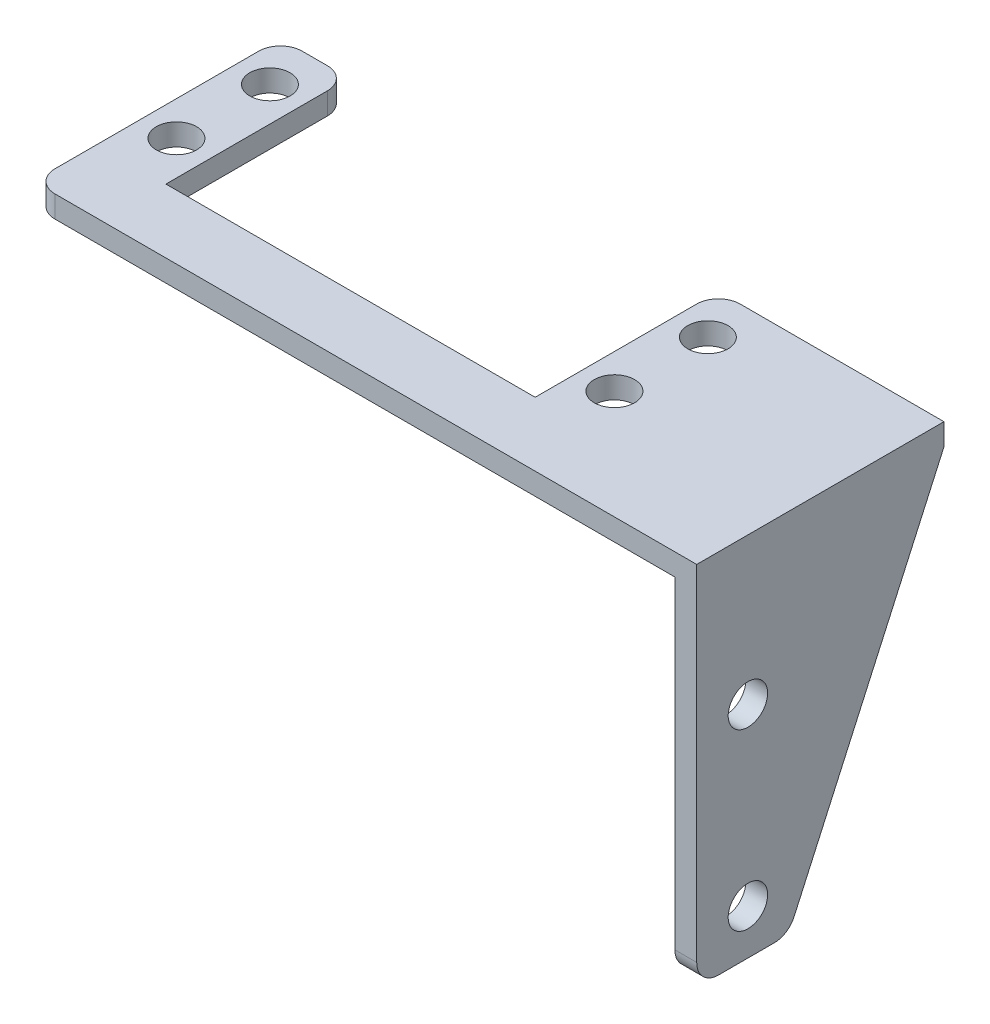
SolidWorks part; units mm, degrees
ref_plane "Front Plane" through (0, 0, 0) normal (0, 0, 1) x (1, 0, 0)
ref_plane "Top Plane" through (0, 0, 0) normal (0, 1, 0) x (1, 0, 0)
ref_plane "Right Plane" through (0, 0, 0) normal (1, 0, 0) x (0, 0, -1)
sketch "Sketch1" plane through (0, 0, 0) normal (0, 1, 0) x (1, 0, 0)
  line L0 (20.15, 0) -> (-20.15, 0)
  line L1 (-20.15, 0) -> (-20.15, 20)
  line L2 (-20.15, 20) -> (-27.65, 20)
  line L3 (-27.65, 20) -> (-27.65, -6.985)
  line L4 (-27.65, -6.985) -> (27.65, -6.985)
  line L5 (0, 0) -> (0, -6.985)
  line L6 (20.15, 20) -> (42.3837, 20)
  line L7 (42.3837, 20) -> (42.3837, -6.985)
  line L8 (20.15, 0) -> (20.15, 20)
  line L9 (27.65, -6.985) -> (42.3837, -6.985)
  circle A0 centre (-23.9, 15.1) radius 2.2
  circle A1 centre (-23.9, 4.9) radius 2.2
  circle A2 centre (23.9, 4.9) radius 2.2
  circle A3 centre (23.9, 15.1) radius 2.2
  point P0 (0, 0)
  dimension "D3" = 4.4
  dimension "D6" = 4.4
  dimension "D1" = 3.75
  dimension "D2" = 3.75
  dimension "D4" = 4.9
  dimension "D5" = 10.2
  dimension "D7" = 4.9
  dimension "D8" = 6.985
  dimension "D9" = 23.9
  dimension "D10" = 0
  dimension "D11" = 22.2338
extrude "Boss-Extrude1" add sketch "Sketch1" along normal blind 2.3813 contours L5 L0 L1 L2 L3 L4 A1 A0 | L8 L0 L5 L4 A2 A3 region at (27.3831, 0, -4.3765) region at (-0.3864, 0, 3.4925)
sketch "Sketch3" plane through (42.3837, 0, 0) normal (1, 0, 0) x (0, 0, -1)
  line L0 (20, 0) -> (3.015, -37.6187)
  line L1 (20, 2.3813) -> (-6.985, 2.3813)
  line L2 (20, 2.3813) -> (20, 0)
  line L3 (3.015, -37.6187) -> (-6.985, -37.6187)
  line L4 (-6.985, 2.3813) -> (-6.985, -37.6187)
  line L5 (-6.985, 2.3813) -> (-6.985, 0) construction
  point P10 (-6.985, 1.1906)
  dimension "D1" = 10
  dimension "D2" = 0
  dimension "D3" = 40
extrude "Boss-Extrude3" add sketch "Sketch3" along normal blind 2.3813
sketch "Sketch4" plane through (44.765, 0, 0) normal (1, 0, 0) x (0, 0, -1)
  line L0 (20, 2.3813) -> (-6.985, 2.3813) construction
  line L1 (-6.985, 2.3813) -> (-6.985, -37.6187) construction
  circle A0 centre (-1.397, -13.646) radius 2.1526
  circle A1 centre (-1.397, -32.696) radius 2.1526
  dimension "D4" = 4.3053
  dimension "D5" = 4.3053
  dimension "D1" = 16.0272
  dimension "D2" = 5.588
  dimension "D3" = 19.05
  dimension "D6" = 5.588
extrude "Cut-Extrude1" cut sketch "Sketch4" against normal up to surface (2.3813 mm away) up to face at (42.3837, -18.8094, -2.2613)
fillet "Fillet2" radius 2.3813 6 edges at (20.15, 1.1906, -20) (-20.15, 1.1906, -20) (-27.65, 1.1906, 6.985) (-27.65, 1.1906, -20) (43.5744, -37.6187, 6.985) (43.5744, -37.6187, -3.015)
